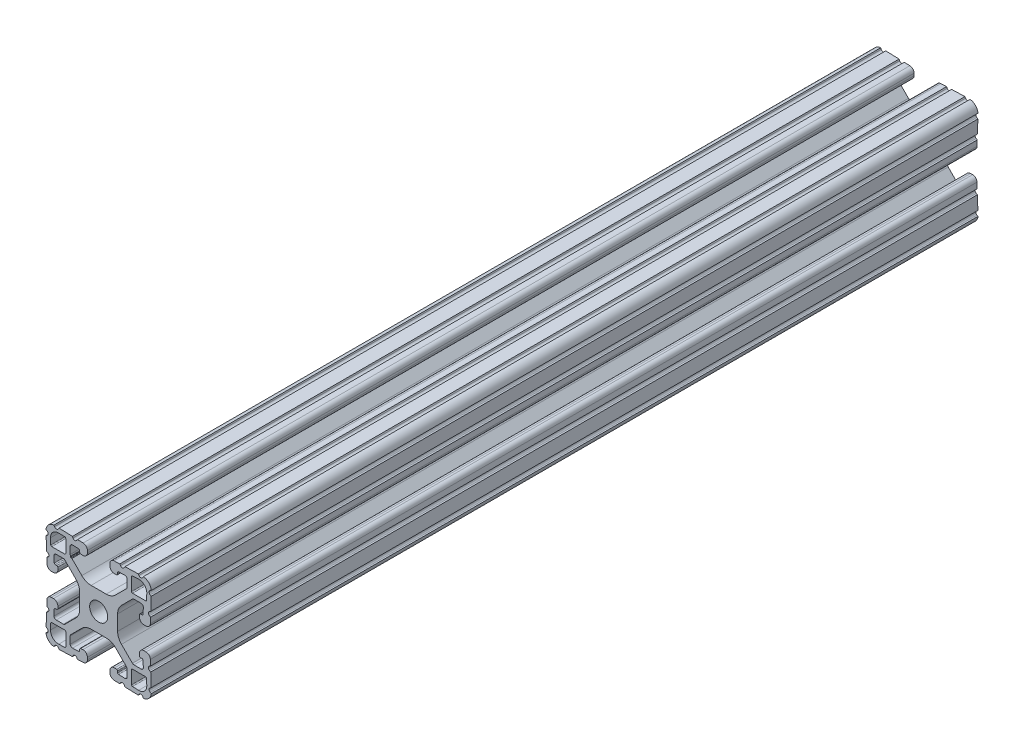
SolidWorks part; units mm, degrees
ref_plane "Front Plane" through (0, 0, 0) normal (0, 0, 1) x (1, 0, 0)
ref_plane "Top Plane" through (0, 0, 0) normal (0, 1, 0) x (1, 0, 0)
ref_plane "Right Plane" through (0, 0, 0) normal (1, 0, 0) x (0, 0, -1)
sketch "Sketch2" plane through (0, 0, 0) normal (0, 0, 1) x (1, 0, 0)
  line L0 (0, 19.05) -> (0, -19.05) construction
  line L1 (-19.05, 0) -> (19.05, 0) construction
  line L2 (4.064, -19.05) -> (19.05, -19.05) construction
  line L3 (19.05, -19.05) -> (19.05, -4.064) construction
  line L4 (4.064, -19.05) -> (4.064, -15.8768) construction
  line L5 (4.064, -15.8768) -> (13.7215, -15.8768) construction
  line L6 (13.7215, -15.8768) -> (4.7027, -6.858) construction
  line L7 (0, 0) -> (19.05, -19.05) construction
  line L8 (19.05, -4.064) -> (15.8768, -4.064) construction
  line L9 (15.8768, -4.064) -> (15.8768, -13.7215) construction
  line L10 (15.8768, -13.7215) -> (6.858, -4.7027) construction
  line L11 (11.3674, -9.2121) -> (9.2121, -11.3674) construction
  line L12 (10.287, -12.4423) -> (10.287, -15.8768) construction
  line L13 (15.7642, -19.0481) -> (4.064, -18.6395) construction
  line L14 (4.064, -18.6395) -> (4.2014, -14.7049) construction
  line L15 (4.2014, -14.7049) -> (6.858, -14.7977) construction
  line L16 (6.858, -14.7977) -> (6.858, -15.8768) construction
  line L17 (19.05, 4.064) -> (19.05, -4.064) construction
  line L18 (-19.05, -19.05) -> (19.05, -19.05) construction
  line L19 (-19.05, -19.05) -> (-19.05, 19.05) construction
  line L20 (-19.05, 19.05) -> (19.05, 19.05) construction
  line L21 (19.05, -19.05) -> (19.05, 19.05) construction
  line L22 (8.5725, -18.7969) -> (8.6004, -17.9973) construction
  line L23 (15.24, -19.0298) -> (15.2679, -18.2301) construction
  circle A0 centre (0, 0) radius 3.2639 construction
  arc A1 (18.1201, -18.1201) -> (15.7642, -19.0481) centre (15.875, -15.875) cw construction
  point P8 (0, -6.858)
  point P16 (10.2898, -10.2898)
  point P28 (11.8872, -11.8872)
  point P34 (8.5725, -18.7969)
  point P36 (15.24, -19.0298)
  point P38 (19.05, 0)
  dimension "D7" = 1.6002
  dimension "Center Hole Diameter" = 6.5278
  dimension "Corner Radius" = 3.175
  dimension "Slot Depth" = 12.192
  dimension "D1" = 3.048
  dimension "D3" = 2
  dimension "Flange Thickness" = 3.937
  dimension "D4" = 3.1732
  dimension "D2" = 20.574
  dimension "D5" = 13.716
  dimension "D6" = 7.1628
  dimension "D8" = 15.24
  dimension "D9" = 8.5725
  dimension "D10" = 0.8001
  dimension "Rail Height" = 38.1
  dimension "Rail Width" = 38.1
  dimension "T Slot Width" = 8.128
sketch "Sketch3" plane through (0, 0, 0) normal (1, 0, 0) x (0, 0, -1)
  line L0 (-149.4498, 19.05) -> (149.4498, 19.05) construction
  line L1 (-98.6498, 0) -> (98.6498, 0) construction
  dimension "Length" = 298.8996
sketch "Sketch4" plane through (0, 0, 0) normal (0, 0, 1) x (1, 0, 0)
  line L1 (6.858, -14.7977) -> (6.858, -15.8768) construction
  line L2 (11.8872, -12.2682) -> (11.8872, -16.9436)
  line L3 (12.2549, -17.3243) -> (14.4454, -17.4008)
  line L7 (12.2682, -11.8872) -> (16.9436, -11.8872)
  line L9 (17.3243, -12.2549) -> (17.4008, -14.4454)
  line L22 (0, 0) -> (19.05, -19.05) construction
  line L23 (15.7642, -19.0481) -> (5.5961, -18.693)
  line L24 (4.064, -17.1065) -> (4.064, -16.344)
  line L25 (5.7069, -14.7575) -> (6.4903, -14.7848)
  line L26 (6.858, -15.1656) -> (6.858, -15.6891)
  line L27 (7.2257, -16.0699) -> (9.4655, -16.1481)
  line L28 (10.287, -15.3549) -> (10.287, -12.771)
  line L29 (10.0545, -12.2098) -> (6.0939, -8.2492)
  line L30 (2.7353, -6.858) -> (0, -6.858)
  line L31 (13.7215, -15.8768) -> (4.7027, -6.858) construction
  line L32 (4.064, -19.05) -> (19.05, -19.05) construction
  line L33 (4.064, -19.05) -> (4.064, -15.8768) construction
  line L34 (0, 19.05) -> (0, -19.05) construction
  line L35 (0, -3.2639) -> (0, -6.858)
  line L36 (0, 0) -> (19.1669, -19.1669) construction
  line L46 (10.287, -12.4423) -> (10.287, -15.8768) construction
  line L47 (6.858, -2.7353) -> (6.858, 0)
  line L48 (12.2098, -10.0545) -> (8.2492, -6.0939)
  line L49 (15.3549, -10.287) -> (12.771, -10.287)
  line L50 (16.0699, -7.2257) -> (16.1481, -9.4655)
  line L51 (15.1656, -6.858) -> (15.6891, -6.858)
  line L52 (14.7575, -5.7069) -> (14.7848, -6.4903)
  line L53 (17.1065, -4.064) -> (16.344, -4.064)
  line L54 (19.0481, -15.7642) -> (18.693, -5.5961)
  line L55 (3.2639, 0) -> (6.858, 0)
  arc A1 (14.4454, -17.4008) -> (17.4008, -14.4454) centre (14.5451, -14.5451) ccw
  arc A10 (16.9436, -11.8872) -> (17.3243, -12.2549) centre (16.9436, -12.2682) cw
  arc A12 (19.0481, -15.7642) -> (15.7642, -19.0481) centre (15.875, -15.875) cw
  arc A13 (3.2639, 0) -> (0, -3.2639) centre (0, 0) cw
  circle A14 centre (0, 0) radius 3.2639 construction
  arc A16 (6.0939, -8.2492) -> (2.7353, -6.858) centre (2.7353, -11.6078) ccw
  arc A17 (5.5961, -18.693) -> (4.064, -17.1065) centre (5.6515, -17.1065) cw
  arc A18 (4.064, -16.344) -> (5.7069, -14.7575) centre (5.6515, -16.344) cw
  arc A19 (9.4655, -16.1481) -> (10.287, -15.3549) centre (9.4933, -15.3549) ccw
  arc A20 (10.287, -12.771) -> (10.0545, -12.2098) centre (9.4933, -12.771) ccw
  arc A21 (6.4903, -14.7848) -> (6.858, -15.1656) centre (6.477, -15.1656) cw
  arc A22 (6.858, -15.6891) -> (7.2257, -16.0699) centre (7.239, -15.6891) ccw
  arc A23 (15.6891, -6.858) -> (16.0699, -7.2257) centre (15.6891, -7.239) cw
  arc A24 (14.7848, -6.4903) -> (15.1656, -6.858) centre (15.1656, -6.477) ccw
  arc A25 (12.771, -10.287) -> (12.2098, -10.0545) centre (12.771, -9.4933) cw
  arc A26 (16.1481, -9.4655) -> (15.3549, -10.287) centre (15.3549, -9.4933) cw
  arc A27 (16.344, -4.064) -> (14.7575, -5.7069) centre (16.344, -5.6515) ccw
  arc A28 (18.693, -5.5961) -> (17.1065, -4.064) centre (17.1065, -5.6515) ccw
  arc A29 (8.2492, -6.0939) -> (6.858, -2.7353) centre (11.6078, -2.7353) cw
  arc A30 (15.7642, -19.0481) -> (18.1201, -18.1201) centre (15.875, -15.875) ccw construction
  arc A31 (11.8872, -12.2682) -> (12.2682, -11.8872) centre (12.2682, -12.2682) cw
  arc A32 (11.8872, -16.9436) -> (12.2549, -17.3243) centre (12.2682, -16.9436) ccw
  point P33 (4.064, -18.6395)
  point P42 (6.858, -4.7027)
  point P45 (4.7027, -6.858)
  point P76 (18.6395, -4.064)
  point P89 (11.8872, -11.8872)
  dimension "D2" = 4.7498
  dimension "D3" = 0.7937
  dimension "D5" = 0.381
  dimension "D6" = 1.5875
  dimension "D8" = 2.8575
  dimension "D4" = 2.6784
  dimension "D7" = 1.6002
extrude "Boss-Extrude1" add sketch "Sketch4" along normal mid plane 298.8996
sketch "Sketch8" plane through (0, 0, 0) normal (0, 0, 1) x (1, 0, 0)
  line L0 (7.6492, -18.7647) -> (9.4958, -18.8292)
  line L1 (15.7642, -19.0481) -> (4.064, -18.6395) construction
  line L2 (9.4958, -18.8292) -> (9.2789, -18.4213)
  line L3 (7.894, -18.3729) -> (7.6492, -18.7647)
  line L4 (8.5725, -18.7969) -> (8.6004, -17.9973) construction
  line L5 (14.3167, -18.9975) -> (16.1633, -19.062)
  line L7 (16.1633, -19.062) -> (15.9464, -18.6541)
  line L8 (14.5615, -18.6058) -> (14.3167, -18.9975)
  line L9 (15.24, -19.0298) -> (15.2679, -18.2301) construction
  line L10 (0, 0) -> (19.05, -19.05) construction
  line L11 (18.6058, -14.5615) -> (18.9975, -14.3167)
  line L12 (19.062, -16.1633) -> (18.6541, -15.9464)
  line L13 (18.9975, -14.3167) -> (19.062, -16.1633)
  line L14 (18.3729, -7.894) -> (18.7647, -7.6492)
  line L15 (18.8292, -9.4958) -> (18.4213, -9.2789)
  line L16 (18.7647, -7.6492) -> (18.8292, -9.4958)
  arc A0 (9.2789, -18.4213) -> (7.894, -18.3729) centre (8.5725, -18.7969) ccw
  arc A1 (15.9464, -18.6541) -> (14.5615, -18.6058) centre (15.24, -19.0298) ccw
  arc A2 (18.6541, -15.9464) -> (18.6058, -14.5615) centre (19.0298, -15.24) cw
  arc A3 (18.4213, -9.2789) -> (18.3729, -7.894) centre (18.7969, -8.5725) cw
  dimension "D1" = 60
extrude "Cut-Extrude2" cut sketch "Sketch8" against normal through all both and the other way through all
mirror "Mirror1" about plane through (0, 0, 0) normal (1, 0, 0) of bodies 142 134
mirror "Mirror2" about plane through (0, 0, 0) normal (0, 1, 0) of bodies 135
sketch "Sketch5" plane through (0, 0, 0) normal (0, 0, 1) x (1, 0, 0)
  line L0 (-6.0939, 8.2492) -> (-10.0545, 12.2098) construction
  line L1 (-10.1338, 12.508) -> (-10.1338, 12)
  line L2 (-9.9645, 11.8306) -> (-9.6506, 11.8306)
  line L3 (-9.6506, 11.8306) -> (-9.6506, 12.508)
  line L4 (-9.6506, 12.508) -> (-10.1338, 12.508)
  line L5 (-9.9046, 12.0598) -> (-9.9645, 12) construction
  circle A0 centre (-9.9046, 12.0598) radius 0.254 construction
  arc A1 (-10.287, 12.771) -> (-10.0545, 12.2098) centre (-9.4933, 12.771) ccw construction
  arc A2 (-10.1338, 12) -> (-9.9645, 11.8306) centre (-9.9645, 12) ccw
  dimension "D3" = 0.1693
  dimension "D1" = 0.7112
  dimension "D4" = 0.508
extrude "Cut-Extrude1" cut sketch "Sketch5" against normal through all both and the other way through all
ref_plane "Plane1" through (0, 19.05, 0) normal (0, 1, 0) x (-1, 0, 0)
ref_plane "Plane2" through (19.05, 0, 0) normal (1, 0, 0) x (0, 0, -1)
ref_plane "Plane3" through (0, -19.05, 0) normal (0, -1, 0) x (1, 0, 0)
ref_plane "Plane4" through (-19.05, 0, 0) normal (-1, 0, 0) x (0, 0, 1)
ref_plane "Plane5" through (-19.038, 0, 0) normal (-1, 0, 0) x (0, 0, 1)
sketch "Sketch10" plane through (-19.038, 0, 0) normal (-1, 0, 0) x (0, 0, 1)
  line L0 (-57.15, 0) -> (57.15, 0)
  point P4 (0, 0)
  dimension "D1" = 114.3
equation "\"D1@Boss-Extrude1\"=\"Length@Sketch3\""
equation "\"D6@Sketch4\"=\"Corner Radius@Sketch2\"/2"
equation "\"D3@Sketch4\"=\"D6@Sketch4\"/2"
equation "\"D4@Sketch2\"=\"Flange Thickness@Sketch2\"*.806"
equation "\"D7@Sketch4\"=\"D7@Sketch2\""
equation "\"D8@Sketch4\"=\"Corner Radius@Sketch2\"*.9"
equation "\"D3@Sketch5\"=\"D2@Sketch5\"/3"
equation "\"D4@Sketch5\"=\"D2@Sketch5\""
equation "\"D8@Sketch2\"=\"Rail Width@Sketch2\"*.4"
equation "\"D9@Sketch2\"=\"Rail Width@Sketch2\"*.225"
equation "\"D10@Sketch2\"=\"D7@Sketch2\"/2"
